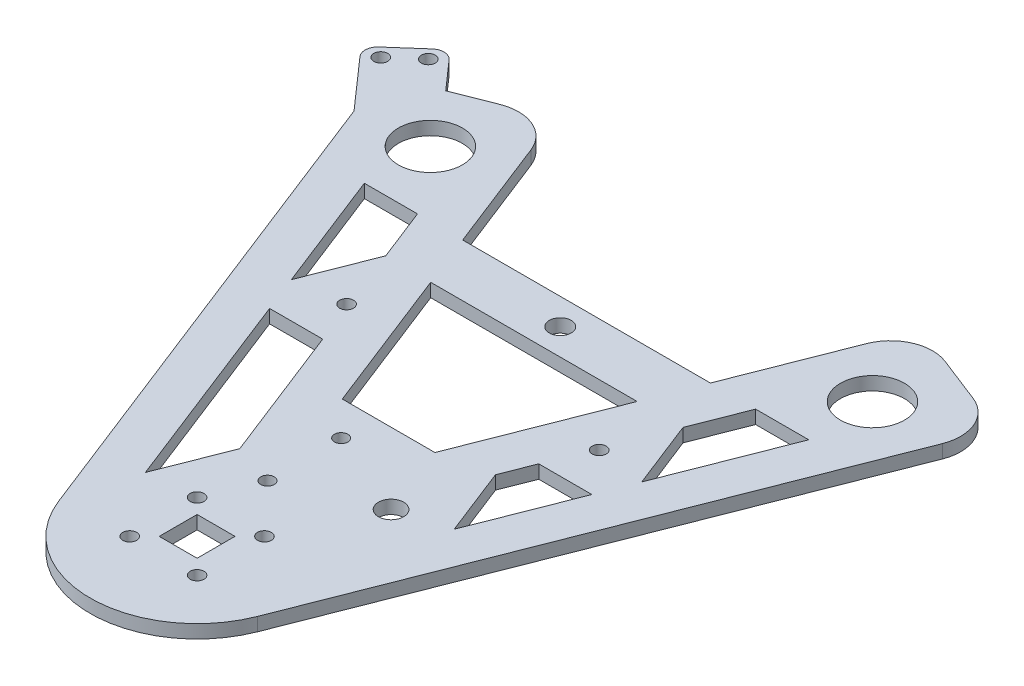
SolidWorks part; units mm, degrees
ref_plane "Front Plane" through (0, 0, 0) normal (0, 0, 1) x (1, 0, 0)
ref_plane "Top Plane" through (0, 0, 0) normal (0, 1, 0) x (1, 0, 0)
ref_plane "Right Plane" through (0, 0, 0) normal (1, 0, 0) x (0, 0, -1)
sketch "Sketch1" plane through (0, 0, 0) normal (0, 1, 0) x (1, 0, 0)
  line L0 (-52.5, 107.9062) -> (52.5, 107.9062) construction
  line L1 (-4.5, -4.5) -> (4.5, -4.5)
  line L2 (-4.5, -4.5) -> (-4.5, 4.5)
  line L3 (-4.5, 4.5) -> (4.5, 4.5)
  line L4 (4.5, -4.5) -> (4.5, 4.5)
  line L5 (-4.5, -4.5) -> (4.5, 4.5) construction
  line L6 (-4.5, 4.5) -> (4.5, -4.5) construction
  line L7 (-73.0716, 116.8972) -> (-23.6501, -9.2645)
  line L8 (23.6501, -9.2645) -> (73.0716, 116.8972)
  line L9 (-43.509, 128.4779) -> (0, 17.4095)
  line L10 (0, 17.4095) -> (43.509, 128.4779)
  line L11 (43.509, 128.4779) -> (73.0716, 116.8972)
  line L12 (-73.0716, 116.8972) -> (-43.509, 128.4779)
  line L13 (-51.2194, 104.6372) -> (-33.5576, 59.5507) construction
  line L14 (-5.0565, -39.0222) -> (18232.1511, 46516.367) construction
  line L15 (-11, 45.4899) -> (11, 45.4899)
  line L16 (17.5, 28.5638) -> (-3.1, 28.5638) construction
  line L17 (-8, -8) -> (8, -8) construction
  line L18 (-8, -8) -> (-8, 8) construction
  line L19 (-8, 8) -> (8, 8) construction
  line L20 (8, -8) -> (8, 8) construction
  line L21 (-8, -8) -> (8, 8) construction
  line L22 (-8, 8) -> (8, -8) construction
  line L23 (-3.1, 37.3138) -> (-3.1, 19.8138) construction
  line L24 (-30, 65.5063) -> (30, 65.5063) construction
  line L25 (-29.4153, 92.5) -> (29.4153, 92.5)
  line L26 (-24.5187, 80) -> (24.5187, 80)
  line L27 (0, 80) -> (0, 92.5) construction
  circle A0 centre (52.5, 107.9062) radius 7.6
  circle A1 centre (-52.5, 107.9062) radius 7.6
  arc A2 (23.6501, -9.2645) -> (-23.6501, -9.2645) centre (0, 0) cw
  circle A6 centre (-30, 65.5063) radius 1.65
  circle A7 centre (30, 65.5063) radius 1.65
  circle A8 centre (17.5, 28.5638) radius 3
  circle A9 centre (-8, 8) radius 1.65
  circle A10 centre (8, 8) radius 1.65
  circle A11 centre (8, -8) radius 1.65
  circle A12 centre (-8, -8) radius 1.65
  circle A13 centre (-3.1, 37.3138) radius 1.6
  circle A14 centre (-3.1, 19.8138) radius 1.6
  circle A15 centre (0, 86.25) radius 2.6
  point P4 (0, 0)
  point P10 (0, 107.9062)
  point P19 (58.2903, 122.6875)
  point P20 (-58.2903, 122.6875)
  point P45 (0, 65.5063)
  point P49 (-3.1, 28.5638)
  point P56 (0, 86.25)
  dimension "D3" = 15.2
  dimension "D7" = 25.4
  dimension "D8" = 3.3
  dimension "D9" = 48
  dimension "D11" = 6
  dimension "D14" = 3.3
  dimension "D17" = 3.2
  dimension "D22" = 5.2
  dimension "D1" = 9
  dimension "D2" = 31.75
  dimension "D4" = 120
  dimension "D5" = 105
  dimension "D6" = 15.875
  dimension "D10" = 22
  dimension "D12" = 39
  dimension "D13" = 16
  dimension "D15" = 20.6
  dimension "D16" = 17.5
  dimension "D18" = 60
  dimension "D19" = 17.5
  dimension "D20" = 12.5
  dimension "D21" = 80
extrude "Boss-Extrude1" add sketch "Sketch1" along normal blind 3.175 contours L7 L8 A2 | A2 L8 L11 L10 L9 L12 L7 A7 A6 A1 A0 L4 L1 L2 L3 | L15 L9 L10 A8 | L9 L26 L10 L25 A15 region at (-57.5163, 0, -120.7116) region at (0, 0, -91.8986) region at (0.0829, 0, -36.0981)
fillet "Fillet1" radius 10 4 edges at (73.0716, 1.5875, -116.8972) (43.509, 1.5875, -128.4779) (-43.509, 1.5875, -128.4779) (-73.0716, 1.5875, -116.8972)
sketch "Sketch2" plane through (0, 3.175, 0) normal (0, 1, 0) x (1, 0, 0)
  line L0 (-38.2766, 55.4899) -> (-25.6572, 55.4899)
  line L1 (-25.6572, 55.4899) -> (-12.9719, 23.1072)
  line L2 (-12.9719, 23.1072) -> (-19.2816, 7)
  line L3 (-19.2816, 7) -> (-38.2766, 55.4899)
  line L8 (-52.7746, 92.5) -> (-41.6102, 64)
  line L9 (-41.6102, 64) -> (-35.3006, 80.1072)
  line L10 (-35.3006, 80.1072) -> (-40.1552, 92.5)
  line L11 (-40.1552, 92.5) -> (-52.7746, 92.5)
  line L12 (-69.4242, 107.5862) -> (-23.6501, -9.2645) construction
  line L13 (-28.7791, 31.245) -> (-38.0901, 27.5975) construction
  line L14 (-47.1924, 78.25) -> (-56.5035, 74.6026) construction
  line L15 (-37.7279, 86.3036) -> (-28.4168, 89.951) construction
  line L16 (-19.3145, 39.2986) -> (-10.0035, 42.946) construction
  line L17 (-24.5187, 80) -> (-11, 45.4899) construction
  line L18 (11, 45.4899) -> (24.5187, 80) construction
  line L19 (-24.5187, 80) -> (24.5187, 80) construction
  line L20 (-29.4153, 92.5) -> (29.4153, 92.5) construction
  line L21 (-11, 45.4899) -> (11, 45.4899) construction
  line L22 (25.6572, 55.4899) -> (38.2766, 55.4899)
  line L23 (38.2766, 55.4899) -> (29.0709, 31.9899)
  line L24 (29.0709, 31.9899) -> (22.7612, 48.0971)
  line L25 (22.7612, 48.0971) -> (25.6572, 55.4899)
  line L26 (40.1552, 92.5) -> (52.7746, 92.5)
  line L27 (52.7746, 92.5) -> (41.6102, 64)
  line L28 (41.6102, 64) -> (35.3006, 80.1072)
  line L29 (35.3006, 80.1072) -> (40.1552, 92.5)
  line L30 (23.6501, -9.2645) -> (69.4242, 107.5862) construction
  line L31 (47.1924, 78.25) -> (56.5035, 74.6026) construction
  line L32 (37.7279, 86.3036) -> (28.4168, 89.951) construction
  line L33 (29.4153, 92.5) -> (39.8615, 119.1668) construction
  dimension "D1" = 10
  dimension "D2" = 10
  dimension "D3" = 16
  dimension "D4" = 7
  dimension "D5" = 13.5
extrude "Cut-Extrude1" cut sketch "Sketch2" against normal through all both and the other way through all
sketch "Sketch3" plane through (0, 0, 0) normal (0, 1, 0) x (1, 0, 0)
  line L0 (-62.1311, 121.183) -> (-70.0656, 130.1854)
  line L1 (-63.7606, 120.5447) -> (-52.8201, 124.8304) construction
  line L2 (-70.0656, 130.1854) -> (-81.3187, 120.2674)
  line L3 (-81.3187, 120.2674) -> (-68.85, 106.1204)
  line L4 (-69.4242, 107.5862) -> (-23.6501, -9.2645) construction
  line L5 (-76.7093, 120.331) -> (-70.7077, 125.6206) construction
  line L6 (-75.6921, 125.2264) -> (-73.7085, 122.9758) construction
  line L7 (-68.85, 106.1204) -> (-69.4242, 107.5862)
  line L8 (-63.7606, 120.5447) -> (-62.1311, 121.183)
  circle A0 centre (-70.7077, 125.6206) radius 1.65
  circle A1 centre (-76.7093, 120.331) radius 1.65
  arc A2 (-69.4242, 107.5862) -> (-63.7606, 120.5447) centre (-60.1131, 111.2336) cw
  arc A3 (-63.7606, 120.5447) -> (-69.4242, 107.5862) centre (-60.1131, 111.2336) ccw construction
  dimension "D5" = 3.3
  dimension "D1" = 110
  dimension "D2" = 15
  dimension "D3" = 12
  dimension "D4" = 10
  dimension "D6" = 8
  dimension "D7" = 3
extrude "Boss-Extrude2" add sketch "Sketch3" along normal up to surface (3.175 mm away) up to face at (28.9415, 3.175, -47.7667)
fillet "Fillet2" radius 3 2 edges at (-81.3187, 1.5875, -120.2674) (-70.0656, 1.5875, -130.1854)
